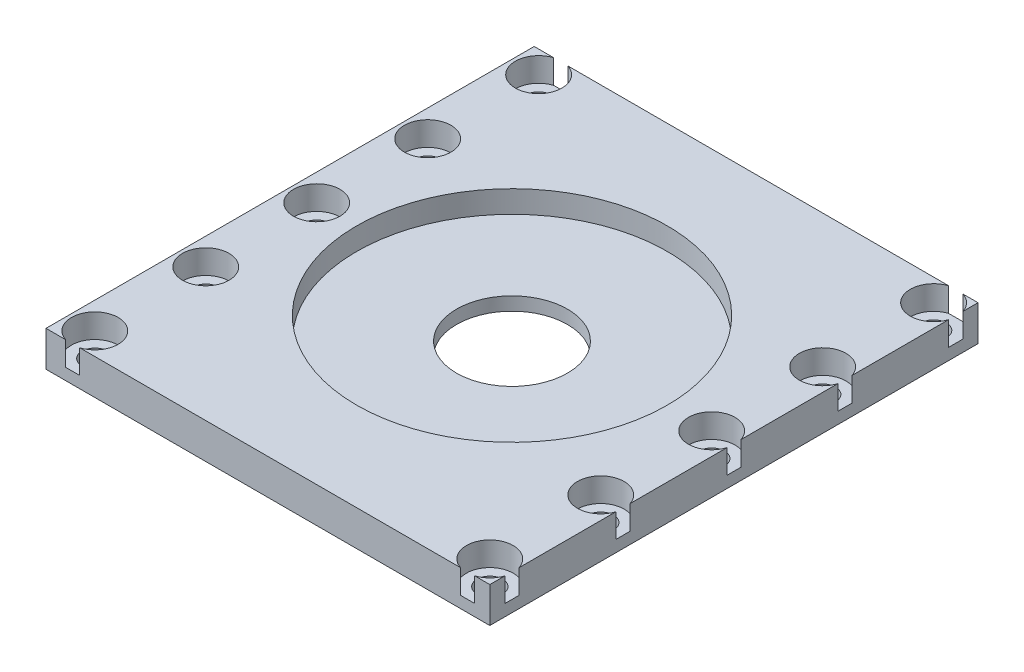
SolidWorks part; units mm, degrees
material "6061-T6 (SS)"
ref_plane "Front Plane" through (0, 0, 0) normal (0, 0, 1) x (1, 0, 0)
ref_plane "Top Plane" through (0, 0, 0) normal (0, 1, 0) x (1, 0, 0)
ref_plane "Right Plane" through (0, 0, 0) normal (1, 0, 0) x (0, 0, -1)
sketch "Sketch1" plane through (0, 0, 0) normal (0, 1, 0) x (1, 0, 0)
  line L1 (0, 0) -> (100, 0)
  line L2 (0, 0) -> (0, 110)
  line L3 (0, 110) -> (100, 110)
  line L4 (100, 0) -> (100, 110)
  dimension "D1" = 110
  dimension "D2" = 100
extrude "Boss-Extrude1" add sketch "Sketch1" along normal blind 8
sketch "Sketch2" plane through (0, 8, 0) normal (0, 1, 0) x (1, 0, 0)
  line L0 (0, 110) -> (6, 110)
  line L1 (100, 110) -> (0, 110) construction
  line L2 (6, 110) -> (6, 0)
  line L3 (0, 0) -> (100, 0) construction
  line L4 (0, 110) -> (0, 0) construction
  line L5 (95, 110) -> (95, 0) construction
  line L7 (100, 0) -> (100, 110) construction
  line L8 (0, 55) -> (6, 55) construction
  point P11 (6, 105)
  point P18 (6, 80)
  point P19 (6, 55)
  point P20 (6, 30)
  point P21 (6, 5)
  point P32 (95, 55)
  point P41 (95, 30)
  point P42 (95, 5)
  point P43 (95, 55)
  point P44 (95, 30)
  point P45 (95, 80)
  point P46 (95, 55)
  point P47 (95, 80)
  point P48 (95, 105)
  dimension "D1" = 5
  dimension "D3" = 6
  dimension "D4" = 5
  dimension "D5" = 3
  dimension "D6" = 3
hole_wizard "CBORE for M5 Hex Socket Head Cap Screw3" positions "Sketch2" profile "Sketch3" counterbore size "M5" standard "DIN"
sketch "Sketch3" plane through (95, 8, -105) normal (1, 0, 0) x (0, 0, 1)
  line L0 (0, 0) -> (0, 9.7425)
  line L1 (0, 9.7425) -> (2.9, 8)
  line L2 (2.9, 8) -> (2.9, 5.4)
  line L3 (2.9, 5.4) -> (5.25, 5.4)
  line L4 (5.25, 5.4) -> (5.25, 0)
  line L5 (5.25, 0) -> (0, 0)
  line L10 (0, 9.7425) -> (-2.9, 8) construction
  line L11 (0, -6.35) -> (0, 107.95) construction
  dimension "Hole Dia." = 5.8
  dimension "Hole Depth" = 8
  dimension "C'Bore Dia." = 10.5
  dimension "C'Bore Depth" = 5.4
  dimension "Drill Angle" = 118
sketch "Sketch6" plane through (0, 8, 0) normal (0, 1, 0) x (1, 0, 0)
  line L2 (100, 110) -> (96.6008, 110) construction
  line L3 (100, 110) -> (0, 0)
  line L4 (0, 0) -> (0, 110)
  line L5 (0, 110) -> (100, 0)
  line L6 (0, 0) -> (4.3992, 0) construction
  point P19 (50, 55)
  point P21 (0, 0)
  point P23 (0, 0)
  point P24 (47.5, 55)
  point P25 (0, 0)
  point P26 (0, 0)
hole_wizard "Ø25.0mm Dowel Hole1" positions "Sketch6" profile "Sketch5" hole size "Ø25.0" standard "DIN"
sketch "Sketch5" plane through (50, 8, -55) normal (1, 0, 0) x (0, 0, 1)
  line L0 (0, 0) -> (0, 17.5108)
  line L1 (0, 17.5108) -> (12.5, 10)
  line L2 (12.5, 10) -> (12.5, 0)
  line L5 (12.5, 0) -> (0, 0)
  line L10 (0, 17.5108) -> (-12.5, 10) construction
  line L11 (0, -6.35) -> (0, 107.95) construction
  dimension "Hole Dia." = 25
  dimension "Hole Depth" = 10
  dimension "Drill Angle" = 118
sketch "Sketch7" plane through (0, 8, 0) normal (0, 1, 0) x (1, 0, 0)
  circle A0 centre (50, 55) radius 35
  dimension "D1" = 70
extrude "Cut-Extrude1" cut sketch "Sketch7" against normal blind 5
